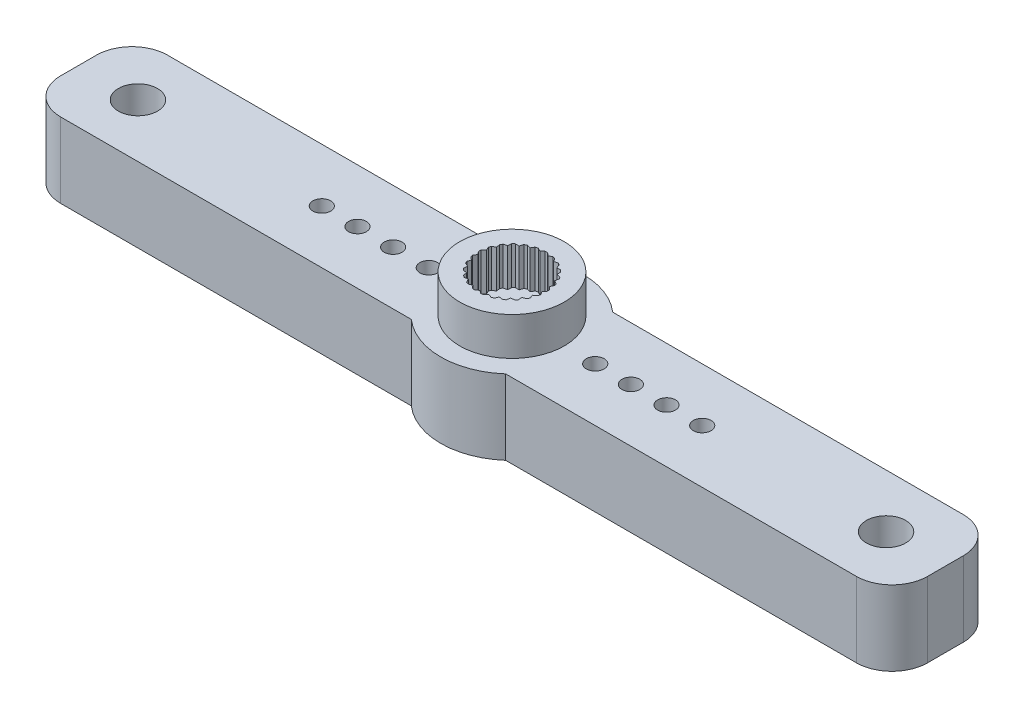
SolidWorks part; units mm, degrees
material "ABS"
ref_plane "Front Plane" through (0, 0, 0) normal (0, 0, 1) x (1, 0, 0)
ref_plane "Top Plane" through (0, 0, 0) normal (0, 1, 0) x (1, 0, 0)
ref_plane "Right Plane" through (0, 0, 0) normal (1, 0, 0) x (0, 0, -1)
sketch "Sketch2" plane through (0, 0, 0) normal (0, 1, 0) x (1, 0, 0)
  circle A0 centre (0, 0) radius 6
  circle A1 centre (0, 0) radius 1.5
  dimension "D1" = 12
  dimension "D2" = 3
extrude "Boss-Extrude1" add sketch "Sketch2" along normal mid plane 2.3
sketch "Sketch3" plane through (0, 1.15, 0) normal (0, 1, 0) x (1, 0, 0)
  line L0 (0, 0) -> (0, 2.9) construction
  line L3 (0, 0) -> (0.376, 2.9763) construction
  line L52 (0.1074, 2.898) -> (0.3384, 2.6787)
  line L53 (-0.1074, 2.898) -> (-0.3384, 2.6787)
  line L54 (0.8248, 2.7802) -> (0.9939, 2.5104)
  line L55 (0.6167, 2.8337) -> (0.3384, 2.6787)
  line L56 (1.4903, 2.4878) -> (1.587, 2.1843)
  line L57 (1.302, 2.5913) -> (0.9939, 2.5104)
  line L58 (2.0621, 2.039) -> (2.0804, 1.721)
  line L59 (1.9055, 2.1861) -> (1.587, 2.1843)
  line L60 (2.5044, 1.4621) -> (2.443, 1.1496)
  line L61 (2.3893, 1.6435) -> (2.0804, 1.721)
  line L62 (2.7894, 0.7934) -> (2.6522, 0.5059)
  line L63 (2.723, 0.9977) -> (2.443, 1.1496)
  line L64 (2.899, 0.0748) -> (2.6947, -0.1695)
  line L65 (2.8855, 0.2892) -> (2.6522, 0.5059)
  line L66 (2.8265, -0.6486) -> (2.5679, -0.8343)
  line L67 (2.8668, -0.4375) -> (2.6947, -0.1695)
  line L68 (2.5765, -1.3311) -> (2.2797, -1.4467)
  line L69 (2.6679, -1.1367) -> (2.5679, -0.8343)
  line L70 (2.1645, -1.93) -> (1.8483, -1.9682)
  line L71 (2.3014, -1.7645) -> (2.2797, -1.4467)
  line L72 (1.6165, -2.4077) -> (1.3007, -2.366)
  line L73 (1.7903, -2.2814) -> (1.8483, -1.9682)
  line L74 (0.967, -2.734) -> (0.6715, -2.6152)
  line L75 (1.1667, -2.655) -> (1.3007, -2.366)
  line L76 (0.2566, -2.8886) -> (0, -2.7)
  line L77 (0.4698, -2.8617) -> (0.6715, -2.6152)
  line L78 (-0.4698, -2.8617) -> (-0.6715, -2.6152)
  line L79 (-0.2566, -2.8886) -> (0, -2.7)
  line L80 (-1.1667, -2.655) -> (-1.3007, -2.366)
  line L81 (-0.967, -2.734) -> (-0.6715, -2.6152)
  line L82 (-1.7903, -2.2814) -> (-1.8483, -1.9682)
  line L83 (-1.6165, -2.4077) -> (-1.3007, -2.366)
  line L84 (-2.3014, -1.7645) -> (-2.2797, -1.4467)
  line L85 (-2.1645, -1.93) -> (-1.8483, -1.9682)
  line L86 (-2.6679, -1.1367) -> (-2.5679, -0.8343)
  line L87 (-2.5765, -1.3311) -> (-2.2797, -1.4467)
  line L88 (-2.8668, -0.4375) -> (-2.6947, -0.1695)
  line L89 (-2.8265, -0.6486) -> (-2.5679, -0.8343)
  line L90 (-2.8855, 0.2892) -> (-2.6522, 0.5059)
  line L91 (-2.899, 0.0748) -> (-2.6947, -0.1695)
  line L92 (-2.723, 0.9977) -> (-2.443, 1.1496)
  line L93 (-2.7894, 0.7934) -> (-2.6522, 0.5059)
  line L94 (-2.3893, 1.6435) -> (-2.0804, 1.721)
  line L95 (-2.5044, 1.4621) -> (-2.443, 1.1496)
  line L96 (-1.9055, 2.1861) -> (-1.587, 2.1843)
  line L97 (-2.0621, 2.039) -> (-2.0804, 1.721)
  line L98 (-1.302, 2.5913) -> (-0.9939, 2.5104)
  line L99 (-1.4903, 2.4878) -> (-1.587, 2.1843)
  line L100 (-0.6167, 2.8337) -> (-0.3384, 2.6787)
  line L101 (-0.8248, 2.7802) -> (-0.9939, 2.5104)
  line L102 (-2.533, 1.6075) -> (-2.3893, 1.6435) construction
  line L103 (-2.533, 1.6075) -> (-2.5044, 1.4621) construction
  line L104 (-2.8532, 0.9271) -> (-2.723, 0.9977) construction
  line L105 (-2.8532, 0.9271) -> (-2.7894, 0.7934) construction
  line L106 (-2.9941, 0.1884) -> (-2.8855, 0.2892) construction
  line L107 (-2.9941, 0.1884) -> (-2.899, 0.0748) construction
  line L108 (-2.9469, -0.5621) -> (-2.8668, -0.4375) construction
  line L109 (-2.9469, -0.5621) -> (-2.8265, -0.6486) construction
  line L110 (0, 3) -> (0.1074, 2.898) construction
  line L111 (0, 2.9) -> (0, 3) construction
  line L112 (0, 3) -> (-0.1074, 2.898) construction
  line L113 (-0.7461, 2.9057) -> (-0.6167, 2.8337) construction
  line L114 (-0.7461, 2.9057) -> (-0.8248, 2.7802) construction
  line L115 (-1.4453, 2.6289) -> (-1.302, 2.5913) construction
  line L116 (-1.4453, 2.6289) -> (-1.4903, 2.4878) construction
  line L117 (-2.0536, 2.1869) -> (-1.9055, 2.1861) construction
  line L118 (-2.0536, 2.1869) -> (-2.0621, 2.039) construction
  line L119 (-2.7145, -1.2773) -> (-2.6679, -1.1367) construction
  line L120 (-2.7145, -1.2773) -> (-2.5765, -1.3311) construction
  line L121 (-2.3115, -1.9123) -> (-2.3014, -1.7645) construction
  line L122 (-2.3115, -1.9123) -> (-2.1645, -1.93) construction
  line L123 (-1.7634, -2.4271) -> (-1.7903, -2.2814) construction
  line L124 (-1.7634, -2.4271) -> (-1.6165, -2.4077) construction
  line L125 (-1.1044, -2.7893) -> (-1.1667, -2.655) construction
  line L126 (-1.1044, -2.7893) -> (-0.967, -2.734) construction
  line L127 (-0.376, -2.9763) -> (-0.4698, -2.8617) construction
  line L128 (-0.376, -2.9763) -> (-0.2566, -2.8886) construction
  line L129 (0.376, -2.9763) -> (0.2566, -2.8886) construction
  line L130 (0.376, -2.9763) -> (0.4698, -2.8617) construction
  line L131 (1.1044, -2.7893) -> (0.967, -2.734) construction
  line L132 (1.1044, -2.7893) -> (1.1667, -2.655) construction
  line L133 (1.7634, -2.4271) -> (1.6165, -2.4077) construction
  line L134 (1.7634, -2.4271) -> (1.7903, -2.2814) construction
  line L135 (2.3115, -1.9123) -> (2.3014, -1.7645) construction
  line L136 (2.3115, -1.9123) -> (2.1645, -1.93) construction
  line L137 (2.7145, -1.2773) -> (2.6679, -1.1367) construction
  line L138 (2.7145, -1.2773) -> (2.5765, -1.3311) construction
  line L139 (2.9469, -0.5621) -> (2.8668, -0.4375) construction
  line L140 (2.9469, -0.5621) -> (2.8265, -0.6486) construction
  line L141 (2.9941, 0.1884) -> (2.8855, 0.2892) construction
  line L142 (2.9941, 0.1884) -> (2.899, 0.0748) construction
  line L143 (2.8532, 0.9271) -> (2.723, 0.9977) construction
  line L144 (2.8532, 0.9271) -> (2.7894, 0.7934) construction
  line L145 (2.533, 1.6075) -> (2.3893, 1.6435) construction
  line L146 (2.533, 1.6075) -> (2.5044, 1.4621) construction
  line L147 (2.0536, 2.1869) -> (1.9055, 2.1861) construction
  line L148 (2.0536, 2.1869) -> (2.0621, 2.039) construction
  line L149 (1.4453, 2.6289) -> (1.302, 2.5913) construction
  line L150 (1.4453, 2.6289) -> (1.4903, 2.4878) construction
  line L151 (0.7461, 2.9057) -> (0.6167, 2.8337) construction
  line L152 (0.7461, 2.9057) -> (0.8248, 2.7802) construction
  circle A0 centre (0, 0) radius 4.4
  circle A1 centre (0, 0) radius 3 construction
  circle A2 centre (0, 0) radius 2.7 construction
  arc A3 (-0.6167, 2.8337) -> (-0.8248, 2.7802) centre (0, 0) ccw
  arc A4 (-0.1074, 2.898) -> (-0.6167, 2.8337) centre (0, 0) ccw construction
  arc A5 (-0.8248, 2.7802) -> (-1.302, 2.5913) centre (0, 0) ccw construction
  arc A6 (-1.302, 2.5913) -> (-1.4903, 2.4878) centre (0, 0) ccw
  arc A7 (-1.4903, 2.4878) -> (-1.9055, 2.1861) centre (0, 0) ccw construction
  arc A8 (-1.9055, 2.1861) -> (-2.0621, 2.039) centre (0, 0) ccw
  arc A9 (-2.0621, 2.039) -> (-2.3893, 1.6435) centre (0, 0) ccw construction
  arc A10 (-2.3893, 1.6435) -> (-2.5044, 1.4621) centre (0, 0) ccw
  arc A11 (-2.5044, 1.4621) -> (-2.723, 0.9977) centre (0, 0) ccw construction
  arc A12 (-2.723, 0.9977) -> (-2.7894, 0.7934) centre (0, 0) ccw
  arc A13 (-2.7894, 0.7934) -> (-2.8855, 0.2892) centre (0, 0) ccw construction
  arc A14 (-2.8855, 0.2892) -> (-2.899, 0.0748) centre (0, 0) ccw
  arc A15 (-2.899, 0.0748) -> (-2.8668, -0.4375) centre (0, 0) ccw construction
  arc A16 (-2.8668, -0.4375) -> (-2.8265, -0.6486) centre (0, 0) ccw
  arc A17 (-2.8265, -0.6486) -> (-2.6679, -1.1367) centre (0, 0) ccw construction
  arc A18 (-2.6679, -1.1367) -> (-2.5765, -1.3311) centre (0, 0) ccw
  arc A19 (-2.5765, -1.3311) -> (-2.3014, -1.7645) centre (0, 0) ccw construction
  arc A20 (-2.3014, -1.7645) -> (-2.1645, -1.93) centre (0, 0) ccw
  arc A21 (-2.1645, -1.93) -> (-1.7903, -2.2814) centre (0, 0) ccw construction
  arc A22 (-1.7903, -2.2814) -> (-1.6165, -2.4077) centre (0, 0) ccw
  arc A23 (-1.6165, -2.4077) -> (-1.1667, -2.655) centre (0, 0) ccw construction
  arc A24 (-1.1667, -2.655) -> (-0.967, -2.734) centre (0, 0) ccw
  arc A25 (-0.967, -2.734) -> (-0.4698, -2.8617) centre (0, 0) ccw construction
  arc A26 (-0.4698, -2.8617) -> (-0.2566, -2.8886) centre (0, 0) ccw
  arc A27 (-0.2566, -2.8886) -> (0.2566, -2.8886) centre (0, 0) ccw construction
  arc A28 (0.2566, -2.8886) -> (0.4698, -2.8617) centre (0, 0) ccw
  arc A29 (0.4698, -2.8617) -> (0.967, -2.734) centre (0, 0) ccw construction
  arc A30 (0.967, -2.734) -> (1.1667, -2.655) centre (0, 0) ccw
  arc A31 (1.1667, -2.655) -> (1.6165, -2.4077) centre (0, 0) ccw construction
  arc A32 (1.6165, -2.4077) -> (1.7903, -2.2814) centre (0, 0) ccw
  arc A33 (1.7903, -2.2814) -> (2.1645, -1.93) centre (0, 0) ccw construction
  arc A34 (2.1645, -1.93) -> (2.3014, -1.7645) centre (0, 0) ccw
  arc A35 (2.3014, -1.7645) -> (2.5765, -1.3311) centre (0, 0) ccw construction
  arc A36 (2.5765, -1.3311) -> (2.6679, -1.1367) centre (0, 0) ccw
  arc A37 (2.6679, -1.1367) -> (2.8265, -0.6486) centre (0, 0) ccw construction
  arc A38 (2.8265, -0.6486) -> (2.8668, -0.4375) centre (0, 0) ccw
  arc A39 (2.8668, -0.4375) -> (2.899, 0.0748) centre (0, 0) ccw construction
  arc A40 (2.899, 0.0748) -> (2.8855, 0.2892) centre (0, 0) ccw
  arc A41 (2.8855, 0.2892) -> (2.7894, 0.7934) centre (0, 0) ccw construction
  arc A42 (2.7894, 0.7934) -> (2.723, 0.9977) centre (0, 0) ccw
  arc A43 (2.723, 0.9977) -> (2.5044, 1.4621) centre (0, 0) ccw construction
  arc A44 (2.5044, 1.4621) -> (2.3893, 1.6435) centre (0, 0) ccw
  arc A45 (2.3893, 1.6435) -> (2.0621, 2.039) centre (0, 0) ccw construction
  arc A46 (2.0621, 2.039) -> (1.9055, 2.1861) centre (0, 0) ccw
  arc A47 (1.9055, 2.1861) -> (1.4903, 2.4878) centre (0, 0) ccw construction
  arc A48 (1.4903, 2.4878) -> (1.302, 2.5913) centre (0, 0) ccw
  arc A49 (1.302, 2.5913) -> (0.8248, 2.7802) centre (0, 0) ccw construction
  arc A50 (0.8248, 2.7802) -> (0.6167, 2.8337) centre (0, 0) ccw
  arc A51 (0.3635, 2.8771) -> (0.1074, 2.898) centre (0, 0) ccw construction
  arc A52 (0.1074, 2.898) -> (-0.1074, 2.898) centre (0, 0) ccw
  arc A53 (0.6167, 2.8337) -> (0.3635, 2.8771) centre (0, 0) ccw construction
  point P84 (0, 0)
  dimension "D1" = 8.8
  dimension "D2" = 5.4
  dimension "D3" = 6
  dimension "D6" = 5.8
  dimension "D4" = 7.2
  dimension "D5" = 25
extrude "Boss-Extrude2" add sketch "Sketch3" along normal blind 3.2
sketch "Sketch4" plane through (0, 0, 0) normal (0, 1, 0) x (1, 0, 0)
  line L0 (0, 0) -> (16, 0) construction
  line L1 (3.9686, 4.5) -> (16.8881, 2.4697)
  line L2 (3.9686, -4.5) -> (16.8881, -2.4697)
  line L3 (16, 0) -> (13, 0) construction
  circle A0 centre (0, 0) radius 6 construction
  arc A1 (3.9686, -4.5) -> (3.9686, 4.5) centre (0, 0) ccw
  arc A2 (16.8881, 2.4697) -> (16.8881, -2.4697) centre (16.5, 0) cw
  circle A3 centre (16, 0) radius 0.75
  circle A4 centre (13, 0) radius 0.75
  circle A5 centre (10, 0) radius 0.75
  circle A6 centre (7, 0) radius 0.75
  dimension "D3" = 2.5
  dimension "D5" = 1.5
  dimension "D2" = 9
  dimension "D7" = 3
  dimension "D4" = 0.5
  dimension "D1" = 16
  dimension "D6" = 4
extrude "Boss-Extrude3" add sketch "Sketch4" along normal mid plane 2.3
pattern_circular "CirPattern1" count 2 over 360 about axis through (0, 4.35, 0) along (0, 1, 0) of "Boss-Extrude3"
sketch "Sketch5" [suppressed] plane through (0, 0, 0) normal (0, 1, 0) x (1, 0, 0)
  line L0 (3, 7) -> (-3, 7) construction
  circle A0 centre (0, 0) radius 10
  circle A1 centre (0, 7) radius 0.75
  circle A2 centre (-3, 7) radius 0.75
  circle A3 centre (3, 7) radius 0.75
  circle A4 centre (7, 3) radius 0.75
  circle A5 centre (7, 0) radius 0.75
  circle A6 centre (7, -3) radius 0.75
  circle A7 centre (3, -7) radius 0.75
  circle A8 centre (0, -7) radius 0.75
  circle A9 centre (-3, -7) radius 0.75
  circle A10 centre (-7, -3) radius 0.75
  circle A11 centre (-7, 0) radius 0.75
  circle A12 centre (-7, 3) radius 0.75
  circle A13 centre (0, 0) radius 1.5 construction
  circle A14 centre (0, 0) radius 1.5
  point P8 (0, 7)
  point P31 (0, 0)
  dimension "D1" = 1.5
  dimension "D3" = 2.25
  dimension "D4" = 6
  dimension "D2" = 7
  dimension "D5" = 4
extrude "Boss-Extrude4" [suppressed] add sketch "Sketch5" along normal mid plane 2.3
sketch "Esboço1" plane through (0, 1.15, 0) normal (0, 1, 0) x (1, 0, 0)
  line L0 (-3.9686, 4.5) -> (-28.9686, 4.5)
  line L1 (-3.9686, -4.5) -> (-28.9686, -4.5)
  line L2 (-28.9686, 4.5) -> (-28.9686, -4.5)
  line L3 (3.9686, 4.5) -> (28.9686, 4.5)
  line L4 (-3.9686, 4.5) -> (-16.8881, 2.4697)
  line L5 (-16.8881, -2.4697) -> (-3.9686, -4.5)
  line L6 (3.9686, -4.5) -> (16.8881, -2.4697)
  line L7 (16.8881, 2.4697) -> (3.9686, 4.5)
  line L8 (-3.9686, 4.5) -> (-16.8881, 2.4697)
  line L9 (-16.8881, -2.4697) -> (-3.9686, -4.5)
  line L10 (3.9686, -4.5) -> (16.8881, -2.4697)
  line L11 (16.8881, 2.4697) -> (3.9686, 4.5)
  line L12 (3.9686, -4.5) -> (28.9686, -4.5)
  line L13 (28.9686, -4.5) -> (28.9686, 4.5)
  arc A4 (3.9686, 4.5) -> (-3.9686, 4.5) centre (0, 0) ccw
  arc A5 (-16.8881, 2.4697) -> (-16.8881, -2.4697) centre (-16.5, 0) ccw
  arc A6 (-3.9686, -4.5) -> (3.9686, -4.5) centre (0, 0) ccw
  arc A7 (16.8881, -2.4697) -> (16.8881, 2.4697) centre (16.5, 0) ccw
  arc A9 (-16.8881, 2.4697) -> (-16.8881, -2.4697) centre (-16.5, 0) ccw
  arc A11 (16.8881, -2.4697) -> (16.8881, 2.4697) centre (16.5, 0) ccw
  dimension "D2" = 45.8567
  dimension "D3" = 12.0805
  dimension "D1" = 0
extrude "Ressalto-extrusão1" add sketch "Esboço1" against normal up to surface (2.3 mm away) up to face at (0, -1.15, 0)
sketch "Esboço2" plane through (0, -1.15, 0) normal (0, -1, 0) x (1, 0, 0)
  line L0 (28.9686, -4.5) -> (28.9686, 4.5) construction
  line L1 (28.9686, 4.5) -> (3.9686, 4.5) construction
  line L2 (-28.9686, 4.5) -> (-36.4686, 4.5)
  line L3 (28.9686, 4.5) -> (36.4686, 4.5)
  line L4 (36.4686, 4.5) -> (36.4686, -4.5)
  line L5 (36.4686, -4.5) -> (28.9686, -4.5)
  line L6 (-36.4686, 4.5) -> (-36.4686, -4.5)
  line L7 (-36.4686, -4.5) -> (-28.9686, -4.5)
  line L12 (3.9686, -4.5) -> (28.9686, -4.5)
  line L14 (28.9686, 4.5) -> (3.9686, 4.5)
  line L15 (-3.9686, 4.5) -> (-28.9686, 4.5)
  line L17 (-28.9686, -4.5) -> (-3.9686, -4.5)
  circle A1 centre (-13, 0) radius 0.75
  arc A4 (-3.9686, -4.5) -> (3.9686, -4.5) centre (0, 0) ccw
  arc A5 (3.9686, 4.5) -> (-3.9686, 4.5) centre (0, 0) ccw
  circle A7 centre (-16, 0) radius 0.75
  circle A9 centre (-10, 0) radius 0.75
  circle A11 centre (-7, 0) radius 0.75
  circle A13 centre (0, 0) radius 1.5
  circle A15 centre (7, 0) radius 0.75
  circle A17 centre (10, 0) radius 0.75
  circle A19 centre (13, 0) radius 0.75
  circle A21 centre (16, 0) radius 0.75
  arc M9 (-3.9686, -4.5) -> (3.9686, -4.5) centre (0, 0) ccw
  line M10 (3.9686, -4.5) -> (28.9686, -4.5)
  line M11 (28.9686, -4.5) -> (28.9686, 4.5)
  line M12 (28.9686, 4.5) -> (3.9686, 4.5)
  arc M13 (3.9686, 4.5) -> (-3.9686, 4.5) centre (0, 0) ccw
  line M14 (-3.9686, 4.5) -> (-28.9686, 4.5)
  line M15 (-28.9686, 4.5) -> (-28.9686, -4.5)
  line M16 (-28.9686, -4.5) -> (-3.9686, -4.5)
  circle M17 centre (0, 0) radius 1.5
  circle M18 centre (7, 0) radius 0.75
  circle M19 centre (16, 0) radius 0.75
  circle M20 centre (13, 0) radius 0.75
  circle M21 centre (10, 0) radius 0.75
  circle M22 centre (-7, 0) radius 0.75
  circle M23 centre (-16, 0) radius 0.75
  circle M24 centre (-13, 0) radius 0.75
  circle M25 centre (-10, 0) radius 0.75
  dimension "D1" = 1.5
  dimension "D2" = 1.5
  dimension "D3" = 1.5
  dimension "D4" = 1.5
  dimension "D5" = 1.5
  dimension "D6" = 3
  dimension "D7" = 1.5
  dimension "D8" = 1.5
  dimension "D9" = 1.5
  dimension "D10" = 6
  dimension "D11" = 6
  dimension "D12" = 7.5
  dimension "D13" = 12.9686
  dimension "D14" = 15.9686
  dimension "D15" = 18.9686
  dimension "D16" = 21.9686
  dimension "D17" = 28.9686
  dimension "D18" = 35.9686
  dimension "D19" = 38.9686
  dimension "D20" = 41.9686
  dimension "D21" = 44.9686
  dimension "D22" = 25
  dimension "D23" = 25
  dimension "D24" = 65.4373
  dimension "D25" = 4.5
  dimension "D26" = 32.9373
  dimension "D27" = 32.9373
  dimension "D28" = 4.5
  dimension "D29" = 9
  dimension "D30" = 9
  dimension "D36" = 57.9373
  dimension "D37" = 57.9373
extrude "Ressalto-extrusão2" add sketch "Esboço2" along normal blind 4 contours M16 M9 M10 M11 M12 M13 M14 M15 M17 M19 M21 M23 M25 M24 M22 M20 M18 | L6 L7 L2 M15 | L5 L4 L3 M11 region at (-32.7186, -1.15, 0) region at (-16.4686, -1.15, 3.9083) region at (32.7186, -1.15, 0)
sketch "Esboço3" plane through (0, -5.15, 0) normal (0, -1, 0) x (1, 0, 0)
  line L0 (0, 0) -> (0, -17.028) construction
  circle A0 centre (-31.4686, 0) radius 1.65
  circle A1 centre (31.4686, 0) radius 1.65
  dimension "D1" = 3.3
  dimension "D2" = 31.4686
extrude "Corte-extrusão1" cut sketch "Esboço3" against normal through all
sketch "Esboço4" plane through (0, -1.15, 0) normal (0, 1, 0) x (1, 0, 0)
  line L0 (36.4686, 4.5) -> (28.9686, 4.5) construction
  line L1 (28.9686, 4.5) -> (28.9686, -4.5) construction
  line L2 (28.9686, -4.5) -> (36.4686, -4.5) construction
  line L3 (36.4686, -4.5) -> (36.4686, 4.5) construction
  line L4 (-36.4686, -4.5) -> (-28.9686, -4.5) construction
  line L5 (-28.9686, -4.5) -> (-28.9686, 4.5) construction
  line L6 (-28.9686, 4.5) -> (-36.4686, 4.5) construction
  line L7 (-36.4686, 4.5) -> (-36.4686, -4.5) construction
  line L8 (36.4686, 4.5) -> (28.9686, 4.5)
  line L9 (28.9686, 4.5) -> (28.9686, -4.5)
  line L10 (28.9686, -4.5) -> (36.4686, -4.5)
  line L11 (36.4686, -4.5) -> (36.4686, 4.5)
  line L12 (-36.4686, -4.5) -> (-28.9686, -4.5)
  line L13 (-28.9686, -4.5) -> (-28.9686, 4.5)
  line L14 (-28.9686, 4.5) -> (-36.4686, 4.5)
  line L15 (-36.4686, 4.5) -> (-36.4686, -4.5)
  circle A0 centre (31.4686, 0) radius 1.65 construction
  circle A1 centre (-31.4686, 0) radius 1.65 construction
  circle A2 centre (31.4686, 0) radius 1.65
  circle A3 centre (-31.4686, 0) radius 1.65
extrude "Ressalto-extrusão3" add sketch "Esboço4" along normal up to surface (2.3 mm away) up to face at (0, 1.15, 4.4)
fillet "Filete2" radius 3 4 edges at (36.4686, -2, 4.5) (36.4686, -2, -4.5) (-36.4686, -2, 4.5) (-36.4686, -2, -4.5)
equation "\"N_hole\"= 4"
equation "\"N_horn\"= 2"
equation "\"D6@Sketch4\"=\"N_hole\""
equation "\"D1@CirPattern1\"=\"N_horn\""
equation "\"D1@Sketch4\"=(\"N_hole\" - 1) *3 +7"
